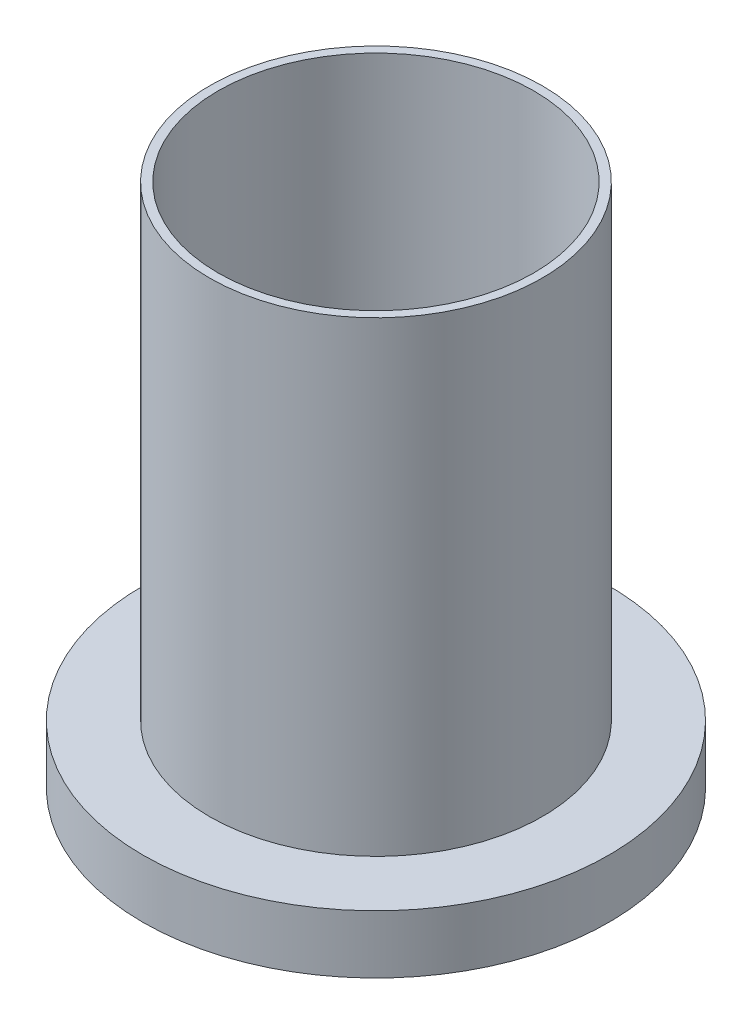
SolidWorks part; units mm, degrees
material "AISI 304"
ref_plane "Front Plane" through (0, 0, 0) normal (0, 0, 1) x (1, 0, 0)
ref_plane "Top Plane" through (0, 0, 0) normal (0, 1, 0) x (1, 0, 0)
ref_plane "Right Plane" through (0, 0, 0) normal (1, 0, 0) x (0, 0, -1)
sketch "Sketch1" plane through (0, 0, 0) normal (0, 1, 0) x (1, 0, 0)
  circle A0 centre (0, 0) radius 30.099
  circle A1 centre (0, 0) radius 31.75
  circle A2 centre (0, 0) radius 44.45
  dimension "D1" = 63.5
  dimension "D2" = 60.198
  dimension "D3" = 88.9
extrude "Boss-Extrude1" add sketch "Sketch1" along normal blind 100.076 contours A1 A0 region at (-30.852, 0, 0)
extrude "Boss-Extrude2" add sketch "Sketch1<4>" along normal blind 11.1125 contours A2 A1 region at (-43.1928, 0, 0)
sketch "Sketch1<4>" plane through (0, 0, 0) normal (0, 1, 0) x (1, 0, 0) same geometry as "Sketch1"
